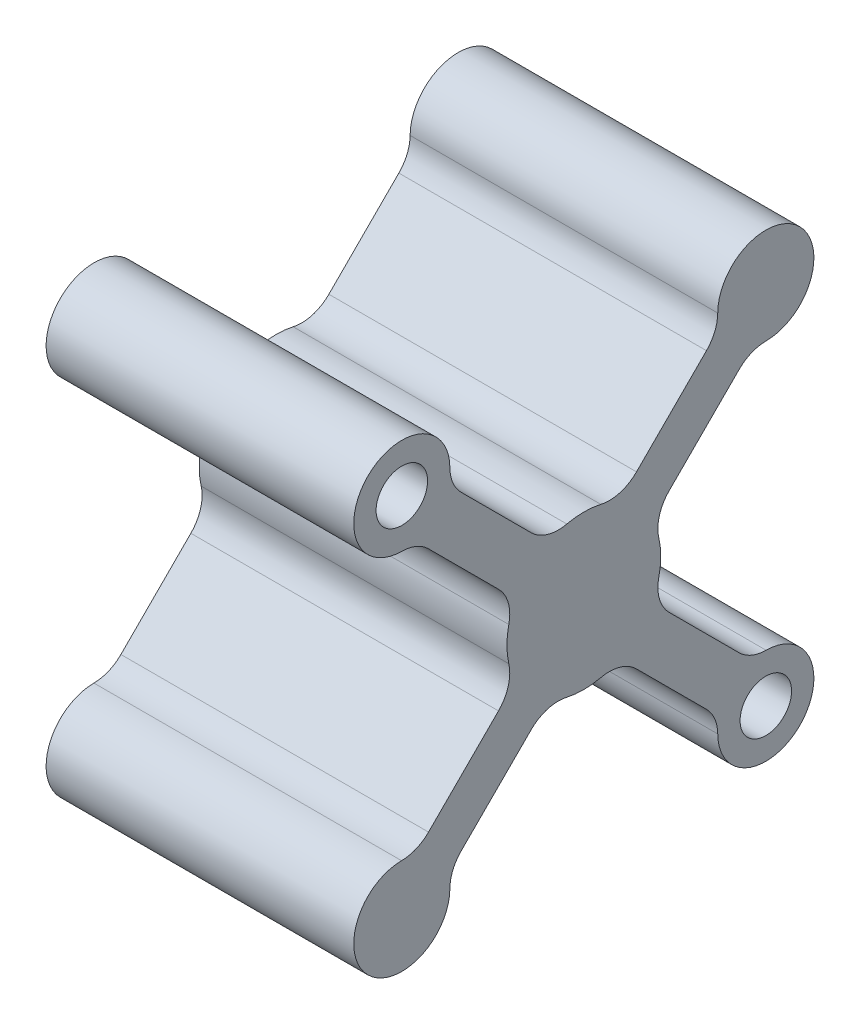
SolidWorks part; units mm, degrees
ref_plane "Front Plane" through (0, 0, 0) normal (1, 0, 0) x (0, 1, 0)
ref_plane "Top Plane" through (0, 0, 0) normal (0, 0, 1) x (0, 1, 0)
ref_plane "Right Plane" through (0, 0, 0) normal (0, 1, 0) x (-1, 0, 0)
sketch "Sketch1" plane through (0, 0, 0) normal (1, 0, 0) x (0, 1, 0)
  line L0 (12.0208, -12.0208) -> (-12.0208, 12.0208) construction
  line L1 (-12.0208, -12.0208) -> (12.0208, 12.0208) construction
  line L2 (0, 0) -> (9.1306, 0) construction
  point P4 (0, 0)
  point P7 (0, 0)
  dimension "D1" = 34
  dimension "D2" = 45
sketch "Sketch2" plane through (0, 0, 0) normal (1, 0, 0) x (0, 1, 0)
  line L0 (12.0208, -12.0208) -> (-12.0208, 12.0208) construction
  line L5 (-8.102, 10.2572) -> (-3.4802, 5.6355)
  line L6 (-12.0208, 12.0208) -> (0, 0) construction
  line L7 (-10.2572, 8.102) -> (-5.6355, 3.4802)
  line L8 (10.2572, 8.102) -> (5.6355, 3.4802)
  line L9 (8.102, 10.2572) -> (3.4802, 5.6355)
  line L10 (8.102, -10.2572) -> (3.4802, -5.6355)
  line L11 (10.2572, -8.102) -> (5.6355, -3.4802)
  line L12 (-10.2572, -8.102) -> (-5.6355, -3.4802)
  line L13 (-8.102, -10.2572) -> (-3.4802, -5.6355)
  circle A0 centre (-12.0208, 12.0208) radius 3.175
  circle A1 centre (12.0208, 12.0208) radius 3.175
  circle A2 centre (12.0208, -12.0208) radius 3.175
  circle A3 centre (-12.0208, -12.0208) radius 3.175
  circle A4 centre (0, 0) radius 5.08
  arc A5 (-8.8459, 12.0388) -> (-8.102, 10.2572) centre (-6.3059, 12.0533) ccw
  arc A6 (-5.6355, 3.4802) -> (-4.9544, 1.1228) centre (-7.4315, 1.6842) cw
  arc A7 (-12.0388, 8.8459) -> (-10.2572, 8.102) centre (-12.0533, 6.3059) cw
  arc A8 (-3.4802, 5.6355) -> (-1.1228, 4.9544) centre (-1.6842, 7.4315) ccw
  arc A9 (12.0388, 8.8459) -> (10.2572, 8.102) centre (12.0533, 6.3059) ccw
  arc A10 (5.6355, 3.4802) -> (4.9544, 1.1228) centre (7.4315, 1.6842) ccw
  arc A11 (8.8459, 12.0388) -> (8.102, 10.2572) centre (6.3059, 12.0533) cw
  arc A12 (3.4802, 5.6355) -> (1.1228, 4.9544) centre (1.6842, 7.4315) cw
  arc A13 (8.8459, -12.0388) -> (8.102, -10.2572) centre (6.3059, -12.0533) ccw
  arc A14 (3.4802, -5.6355) -> (1.1228, -4.9544) centre (1.6842, -7.4315) ccw
  arc A15 (12.0388, -8.8459) -> (10.2572, -8.102) centre (12.0533, -6.3059) cw
  arc A16 (5.6355, -3.4802) -> (4.9544, -1.1228) centre (7.4315, -1.6842) cw
  arc A17 (-12.0388, -8.8459) -> (-10.2572, -8.102) centre (-12.0533, -6.3059) ccw
  arc A18 (-5.6355, -3.4802) -> (-4.9544, -1.1228) centre (-7.4315, -1.6842) ccw
  arc A19 (-8.8459, -12.0388) -> (-8.102, -10.2572) centre (-6.3059, -12.0533) cw
  arc A20 (-3.4802, -5.6355) -> (-1.1228, -4.9544) centre (-1.6842, -7.4315) cw
  point P20 (-5.7911, 7.9464)
  dimension "D1" = 6.35
  dimension "D2" = 10.16
  dimension "D3" = 2.54
  dimension "D4" = 2.54
  dimension "D5" = 1.524
  dimension "D6" = 4
extrude "Boss-Extrude1" add sketch "Sketch2" along normal blind 20.32 contours A0 | A0 L6 A4 A8 L5 A5 | A4 | L9 A12 A4 A10 L8 A9 A1 A11 | A1 | A2 | L11 A16 A4 A14 L10 A13 A2 A15 | L13 A20 A4 A18 L12 A17 A3 A19 | A3 | L6 A0 A7 L7 A6 A4 region at (0, -6.0863, 7.2321) region at (0, -8.9356, 12.0296) region at (0, 0, 4.9363) region at (0, -7.2321, 6.0863) region at (0, 6.6592, 6.6592) region at (0, -6.6592, -6.6592) region at (0, 6.6592, -6.6592) region at (0, 12.0208, 12.0208) region at (0, -12.0208, -12.0208) region at (0, 12.0208, -12.0208)
hole_wizard "M3 Clearance Hole1" positions "Sketch3" profile "Sketch4" hole size "M3" standard "ANSI Metric" end condition through all
sketch "Sketch3" plane through (20.32, 0, 0) normal (1, 0, 0) x (0, 0, -1)
  point P0 (-12.0208, 12.0208)
  point P3 (12.0208, -12.0208)
sketch "Sketch4" plane through (20.32, 12.0208, 12.0208) normal (0, 1, 0) x (0, 0, -1)
  line L0 (0, 0) -> (0, 20.32)
  line L1 (0, 20.32) -> (1.7, 20.32)
  line L2 (1.7, 20.32) -> (1.7, 0)
  line L5 (1.7, 0) -> (0, 0)
  line L11 (0, -6.35) -> (0, 107.95) construction
  dimension "Thru Hole Dia." = 3.4
  dimension "Thru Hole Depth" = 20.32
equation "\"D1@Sketch1\"=34mm"
